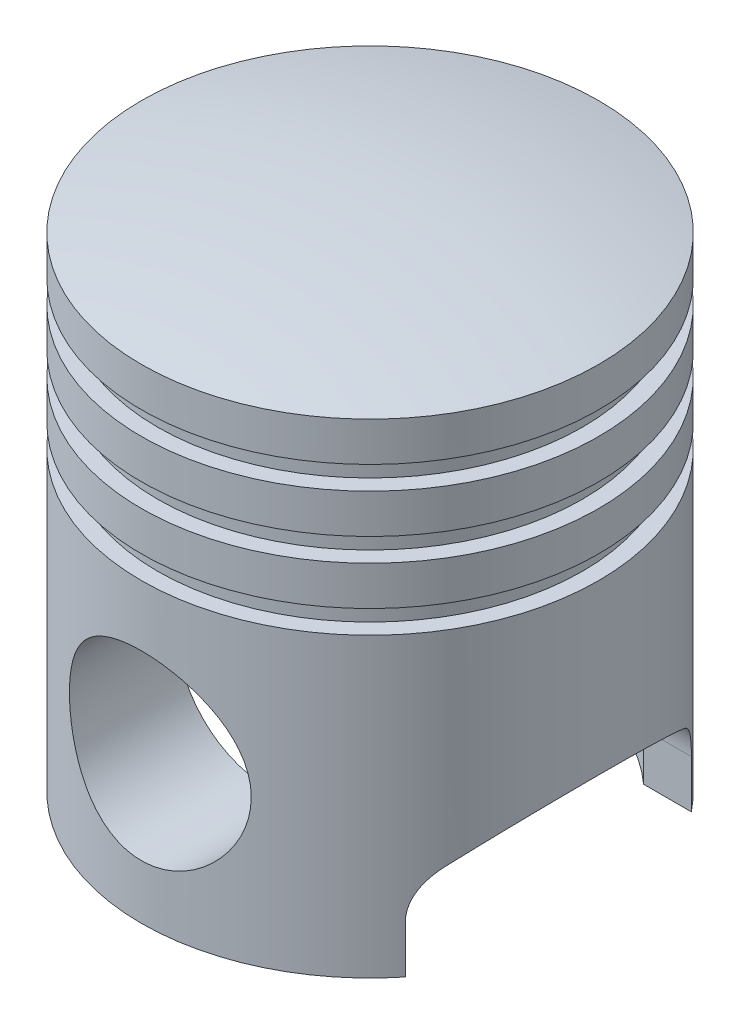
SolidWorks part; units mm, degrees
ref_plane "Front Plane" through (0, 0, 0) normal (0, 0, 1) x (1, 0, 0)
ref_plane "Top Plane" through (0, 0, 0) normal (0, 1, 0) x (1, 0, 0)
ref_plane "Right Plane" through (0, 0, 0) normal (1, 0, 0) x (0, 0, -1)
sketch "Sketch1" plane through (0, 0, 0) normal (0, 1, 0) x (1, 0, 0)
  line L0 (0, 75.7274) -> (0, -92.6092) construction
  line L1 (-165.6837, 0) -> (174.3658, 0) construction
  circle A0 centre (0, 0) radius 42.5
extrude "Boss-Extrude1" add sketch "Sketch1" along normal blind 90
sketch "Sketch2" plane through (0, 0, 0) normal (0, 0, 1) x (1, 0, 0)
  line L0 (0, 126.4283) -> (0, -29.6004) construction
  line L1 (-165.3854, 48.4139) -> (169.6844, 48.4139) construction
sketch "Sketch3" plane through (0, 90, 0) normal (0, 1, 0) x (1, 0, 0)
  line L0 (0, 61.5721) -> (0, -67.3023) construction
  circle A0 centre (0, 0) radius 39.5
extrude "Cut-Extrude1" cut sketch "Sketch3" against normal blind 4.3 from offset 7.3 flip side to cut contours A0 offset against normal yes
pattern_linear "LPattern1" count 3 spacing 11.6 along (0, -1, 0) of "Cut-Extrude1"
sketch "Sketch4" plane through (0, 0, 0) normal (0, -1, 0) x (1, 0, 0)
  circle A0 centre (0, 0) radius 36
extrude "Cut-Extrude2" cut sketch "Sketch4" against normal blind 85
dome "Dome1" faces to dome 1 distance 5 reverse direction no elliptical dome no face at (0, 90, 42.5) parameters "D1"=5
sketch "Sketch5" plane through (0, 0, 0) normal (0, 0, 1) x (1, 0, 0)
  line L0 (0, 0) -> (0, 27) construction
  line L1 (0, 126.4283) -> (0, -29.6004) construction
  circle A0 centre (0, 27) radius 16.9
extrude "Cut-Extrude3" cut sketch "Sketch5" against normal through all and the other way through all
sketch "Sketch6" plane through (0, 0, 0) normal (1, 0, 0) x (0, 0, -1)
  line L0 (-26.5879, 0) -> (26.5879, 0)
  line L1 (-42.5, 0) -> (42.5, 0) construction
  line L2 (26.5879, 0) -> (26.5879, 13.7848)
  line L5 (-26.5879, 0) -> (-26.5879, 13.7848)
  arc A0 (-26.5879, 13.7848) -> (26.5879, 13.7848) centre (0, -16.0997) cw
  point P12 (0, 0)
extrude "Cut-Extrude4" cut sketch "Sketch6" against normal through all both and the other way through all
fillet "Fillet1" radius 10 2 edges at (-28.7136, 13.7848, -26.5879) (-28.7136, 13.7848, 26.5879)
fillet "Fillet2" radius 10 2 edges at (28.7136, 13.7848, 26.5879) (28.7136, 13.7848, -26.5879)
sketch "Sketch8" plane through (0, 0, 0) normal (0, 0, 1) x (1, 0, 0)
  circle A0 centre (0, 27) radius 16.9 construction
  circle A1 centre (0, 27) radius 16.9
  circle A2 centre (0, 27) radius 22.5
extrude "Boss-Extrude2" add sketch "Sketch8" along normal up to next from offset 19
sketch "Sketch9" plane through (0, 0, 0) normal (1, 0, 0) x (0, 0, -1)
  line L0 (0, 118.3956) -> (0, -29.6004) construction
  line L1 (0, 126.4283) -> (0, -29.6004) construction
  point P5 (0, 0)
mirror "Mirror1" about plane through (0, 0, 0) normal (0, 0, 1) of "Boss-Extrude2"
